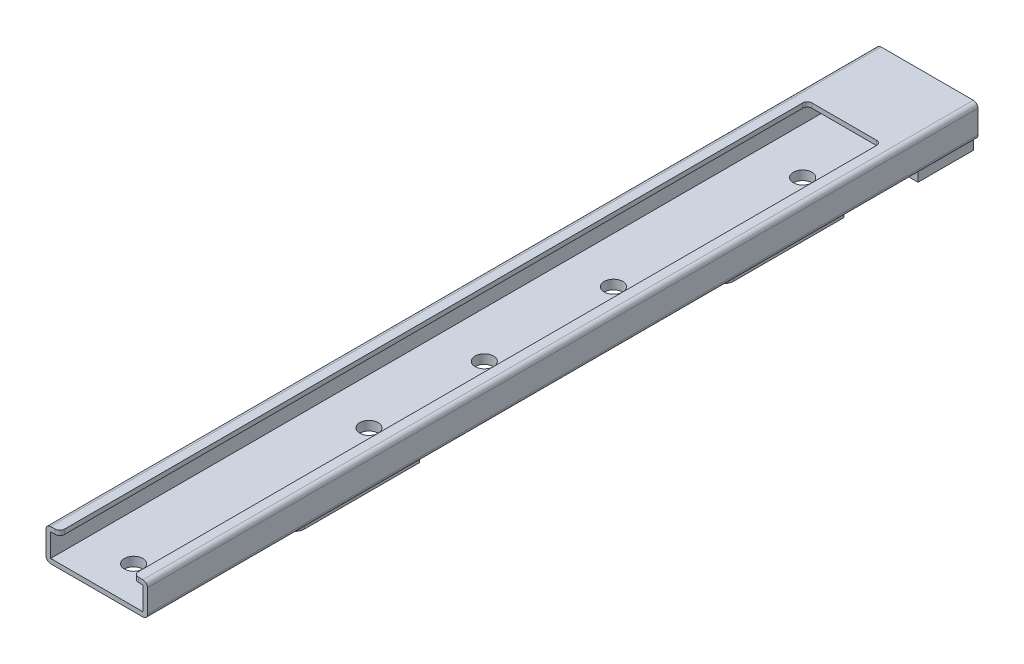
SolidWorks part; units mm, degrees
ref_plane "Front Plane" through (0, 0, 0) normal (0, 0, 1) x (1, 0, 0)
ref_plane "Top Plane" through (0, 0, 0) normal (0, 1, 0) x (1, 0, 0)
ref_plane "Right Plane" through (0, 0, 0) normal (1, 0, 0) x (0, 0, -1)
sketch "Sketch1" plane through (0, 0, 0) normal (0, 1, 0) x (1, 0, 0)
  line L1 (-5.5, -45) -> (5.5, -45)
  line L2 (-5.5, -45) -> (-5.5, 45)
  line L3 (-5.5, 45) -> (5.5, 45)
  line L4 (5.5, -45) -> (5.5, 45)
  line L5 (-5.5, -45) -> (5.5, 45) construction
  line L6 (-5.5, 45) -> (5.5, -45) construction
  point P0 (0, 0)
  dimension "D1" = 90
  dimension "D2" = 11
extrude "Boss-Extrude1" add sketch "Sketch1" along normal blind 3.5
sketch "Sketch2" plane through (0, 0, 45) normal (0, 0, 1) x (1, 0, 0)
  line L0 (-4, 3.5) -> (-4, 3)
  line L1 (-5.5, 3.5) -> (5.5, 3.5) construction
  line L2 (-4, 3) -> (-5, 3)
  line L3 (-5, 3) -> (-5, 0.5)
  line L4 (-5, 0.5) -> (5, 0.5)
  line L5 (5, 0.5) -> (5, 3)
  line L6 (5, 3) -> (4, 3)
  line L7 (4, 3) -> (4, 3.5)
  line L8 (4, 3.5) -> (-4, 3.5)
  line L9 (-5.5, 3.5) -> (-5.5, 0) construction
  line L10 (-5.5, 0) -> (5.5, 0) construction
  dimension "D1" = 10
  dimension "D2" = 2.5
  dimension "D3" = 2.5
  dimension "D4" = 0.5
  dimension "D5" = 1
  dimension "D6" = 1
  dimension "D7" = 0.5
extrude "Cut-Extrude1" cut sketch "Sketch2" against normal blind 81
sketch "Sketch3" plane through (0, 0, -36) normal (0, 0, 1) x (1, 0, 0)
  line L0 (-4, 3) -> (4, 3)
  line L8 (4, 3.5) -> (-4, 3.5)
  line L9 (-4, 3.5) -> (-4, 3)
  line L10 (-4, 3) -> (-5, 3)
  line L11 (-5, 3) -> (-5, 0.5)
  line L12 (-5, 0.5) -> (5, 0.5)
  line L13 (5, 0.5) -> (5, 3)
  line L14 (5, 3) -> (4, 3)
  line L15 (4, 3) -> (4, 3.5)
  line L16 (4, 3.5) -> (-4, 3.5)
  line L17 (-4, 3.5) -> (-4, 3)
  line L18 (-4, 3) -> (-5, 3)
  line L19 (-5, 3) -> (-5, 0.5)
  line L20 (-5, 0.5) -> (5, 0.5)
  line L21 (5, 0.5) -> (5, 3)
  line L22 (5, 3) -> (4, 3)
  line L23 (4, 3) -> (4, 3.5)
  line M11 (-4, 3) -> (-5, 3)
  line M12 (-5, 3) -> (-5, 0.5)
  line M13 (-5, 0.5) -> (5, 0.5)
  line M14 (5, 0.5) -> (5, 3)
  line M15 (5, 3) -> (4, 3)
  dimension "D1" = 0
extrude "Cut-Extrude2" cut sketch "Sketch3" against normal blind 6 contours L0 M11 M12 M13 M14 M15 region at (0, 1.75, -36)
fillet "Fillet1" radius 0.5 4 edges at (5.5, 0, 0) (-5.5, 0, 0) (5.5, 3.5, 0) (-5.5, 3.5, 0)
fillet "Fillet2" radius 0.5 4 edges at (4, 3.25, -36) (-4, 3.25, 45) (4, 3.25, 45) (-4, 3.25, -36)
sketch "Sketch4" plane through (0, 0, 0) normal (0, -1, 0) x (1, 0, 0)
  line L0 (-5, 45) -> (5, 45) construction
  line L1 (5, -45) -> (-5, -45) construction
  line L2 (5, 28.5) -> (-5, 28.5)
  line L3 (5, -45) -> (5, 45) construction
  line L4 (-5, 45) -> (-5, -45) construction
  line L5 (-5, 28.5) -> (-5, 15)
  line L6 (-5, 15) -> (-3.5, 15)
  line L7 (-3.5, 15) -> (-3.5, 18)
  line L8 (-3.5, 18) -> (3.5, 18)
  line L9 (3.5, 18) -> (3.5, 15)
  line L10 (3.5, 15) -> (5, 15)
  line L11 (5, 15) -> (5, 28.5)
  line L12 (5, -18) -> (-5, -18)
  line L13 (-5, -18) -> (-5, -31)
  line L14 (-5, -31) -> (-3.5, -31)
  line L15 (-3.5, -31) -> (-3.5, -28)
  line L16 (-3.5, -28) -> (3.5, -28)
  line L17 (3.5, -28) -> (3.5, -31)
  line L18 (3.5, -31) -> (5, -31)
  line L19 (5, -31) -> (5, -18)
  circle A0 centre (0, -31.5) radius 1
  circle A1 centre (0, -11) radius 1
  circle A2 centre (0, 3) radius 1
  circle A3 centre (0, 15.5) radius 1
  circle A4 centre (0, 41) radius 1
  circle A5 centre (0, -31.5) radius 2
  circle A6 centre (0, -11) radius 2
  circle A7 centre (0, 3) radius 2
  circle A8 centre (0, 41) radius 2
  circle A9 centre (0, 15.5) radius 2
  point P39 (5, -18.4297)
  point P40 (-5, -18.5016)
  point P41 (-5, -30.6458)
  dimension "D6" = 2
  dimension "D7" = 2
  dimension "D8" = 2
  dimension "D9" = 2
  dimension "D10" = 2
  dimension "D11" = 4
  dimension "D12" = 4
  dimension "D13" = 4
  dimension "D14" = 4
  dimension "D15" = 4
  dimension "D1" = 4
  dimension "D2" = 29.5
  dimension "D3" = 12.5
  dimension "D4" = 14
  dimension "D5" = 13.5
  dimension "D16" = 16.5
  dimension "D17" = 30
  dimension "D18" = 30
  dimension "D19" = 1.5
  dimension "D20" = 1.5
  dimension "D21" = 27
  dimension "D22" = 1.5
  dimension "D23" = 1.5
  dimension "D24" = 27
  dimension "D25" = 14
  dimension "D26" = 14
  dimension "D27" = 3
extrude "Boss-Extrude2" add sketch "Sketch4" along normal blind 0.5
extrude "Cut-Extrude3" cut sketch "Sketch4<2>" against normal blind 1 contours A0 | A1 | A2 | A3 | A4 region at (0, 0, -31.5) region at (0, 0, -11) region at (0, 0, 3) region at (0, 0, 15.5) region at (0, 0, 41)
sketch "Sketch4<2>" plane through (0, 0, 0) normal (0, -1, 0) x (1, 0, 0) same geometry as "Sketch4"
fillet "Fillet3" radius 0.5 4 edges at (0, -0.5, -33.5) (0, -0.5, 13.5) (0, -0.5, 1) (0, -0.5, -13)
fillet "Fillet4" radius 1 4 edges at (5, -0.25, -18) (-5, -0.25, -18) (5, -0.25, 28.5) (-5, -0.25, 28.5)
sketch "Sketch5" plane through (0, 0, 0) normal (0, -1, 0) x (1, 0, 0)
  line L0 (-5, -31) -> (-5, -45) construction
  line L1 (5, -45) -> (-5, -45)
  line L2 (5, -45) -> (5, -39)
  line L3 (5, -39) -> (-5, -39)
  line L4 (-5, -45) -> (-5, -39)
  dimension "D1" = 6
extrude "Boss-Extrude3" add sketch "Sketch5" along normal blind 1.2
